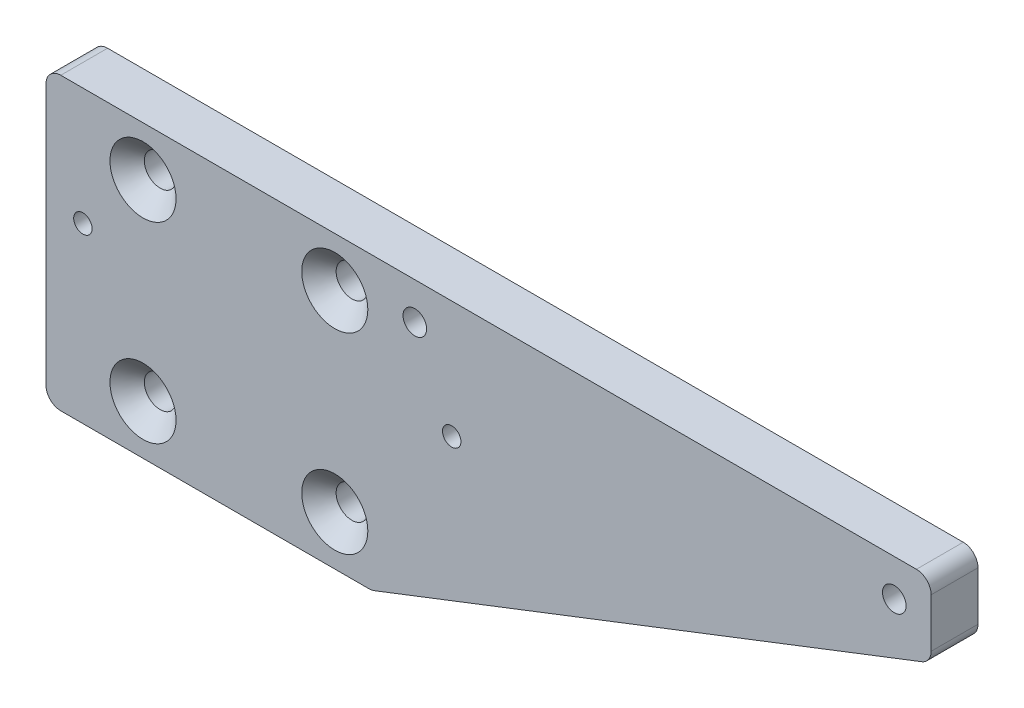
SolidWorks part; units mm, degrees
material "AISI 1045 Steel, cold drawn"
ref_plane "Front Plane" through (0, 0, 0) normal (0, 0, 1) x (1, 0, 0)
ref_plane "Top Plane" through (0, 0, 0) normal (0, 1, 0) x (1, 0, 0)
ref_plane "Right Plane" through (0, 0, 0) normal (1, 0, 0) x (0, 0, -1)
sketch "Sketch1" plane through (0, 0, 0) normal (0, 0, 1) x (1, 0, 0)
  line L0 (22.075, 19.7) -> (97.925, 19.7)
  line L1 (17.075, -13) -> (-8.925, -13) construction
  line L2 (17.075, -13) -> (17.075, 13) construction
  line L3 (17.075, 13) -> (-8.925, 13) construction
  line L4 (-8.925, -13) -> (-8.925, 13) construction
  line L5 (17.075, -13) -> (-8.925, 13) construction
  line L6 (17.075, 13) -> (-8.925, -13) construction
  line L7 (22.075, -19.7) -> (-22.075, -19.7)
  line L8 (22.075, -19.7) -> (22.075, 19.7) construction
  line L9 (22.075, 19.7) -> (-22.075, 19.7)
  line L10 (-22.075, -19.7) -> (-22.075, 19.7)
  line L11 (22.075, -19.7) -> (-22.075, 19.7) construction
  line L12 (22.075, 19.7) -> (-22.075, -19.7) construction
  line L13 (97.925, 19.7) -> (97.925, 9.7)
  line L14 (97.925, 9.7) -> (22.075, -19.7)
  point P0 (4.075, 0)
  point P6 (0, 0)
  point P13 (14.2462, 0.3571)
  dimension "D1" = 39.4
  dimension "D2" = 120
  dimension "D3" = 5
  dimension "D4" = 26
  dimension "D5" = 10
  dimension "D6" = 26.15
extrude "Boss-Extrude1" add sketch "Sketch1" along normal blind 6.35
hole_wizard "CSK for M4 SFHCS2" positions "Sketch2" profile "Sketch3" countersink size "M4" standard "ANSI Metric" end condition through all
sketch "Sketch2" plane through (0, 0, 6.35) normal (0, 0, 1) x (1, 0, 0)
  point P0 (17.075, 13)
  point P3 (-8.925, 13)
sketch "Sketch3" plane through (17.075, 13, 6.35) normal (1, 0, 0) x (0, -1, 0)
  line L0 (0, 0) -> (0, 6.35)
  line L1 (0, 6.35) -> (2.15, 6.35)
  line L2 (2.15, 6.35) -> (2.15, 2.33)
  line L3 (2.15, 2.33) -> (4.48, 0)
  line L5 (4.48, 0) -> (0, 0)
  line L6 (-2.15, 2.33) -> (-4.48, 0) construction
  line L11 (0, -6.35) -> (0, 107.95) construction
  dimension "Thru Hole Dia." = 4.3
  dimension "Thru Hole Depth" = 6.35
  dimension "Near C'Sink Dia." = 8.96
  dimension "Near C'Sink Angle" = 90
hole_wizard "CSK for M4 SFHCS1" positions "Sketch10" profile "Sketch11" countersink size "M4" standard "ANSI Metric" end condition through all
sketch "Sketch10" plane through (0, 0, 6.35) normal (0, 0, 1) x (1, 0, 0)
  point P0 (-8.925, -13)
  point P3 (17.075, -13)
sketch "Sketch11" plane through (-8.925, -13, 6.35) normal (1, 0, 0) x (0, -1, 0)
  line L0 (0, 0) -> (0, 6.35)
  line L1 (0, 6.35) -> (2.15, 6.35)
  line L2 (2.15, 6.35) -> (2.15, 2.33)
  line L3 (2.15, 2.33) -> (4.48, 0)
  line L5 (4.48, 0) -> (0, 0)
  line L6 (-2.15, 2.33) -> (-4.48, 0) construction
  line L11 (0, -6.35) -> (0, 107.95) construction
  dimension "Thru Hole Dia." = 4.3
  dimension "Thru Hole Depth" = 6.35
  dimension "Near C'Sink Dia." = 8.96
  dimension "Near C'Sink Angle" = 90
hole_wizard "Tap Drill for M3x0.5 Tap1" positions "Sketch4" profile "Sketch5" hole size "M3x0.5" standard "ANSI Metric" end condition through all
sketch "Sketch4" plane through (0, 0, 6.35) normal (0, 0, 1) x (1, 0, 0)
  line L0 (-17.075, 3.8) -> (32.925, 3.8) construction
  line L2 (97.925, 19.7) -> (-22.075, 19.7) construction
  line L4 (-22.075, 19.7) -> (-22.075, -19.7) construction
  point P0 (-17.075, 3.8)
  point P2 (32.925, 3.8)
  dimension "D1" = 15.9
  dimension "D2" = 50
  dimension "D3" = 5
sketch "Sketch5" plane through (-17.075, 3.8, 6.35) normal (1, 0, 0) x (0, -1, 0)
  line L0 (0, 0) -> (0, 6.35)
  line L1 (0, 6.35) -> (1.25, 6.35)
  line L2 (1.25, 6.35) -> (1.25, 0)
  line L5 (1.25, 0) -> (0, 0)
  line L11 (0, -6.35) -> (0, 107.95) construction
  dimension "Thru Hole Dia." = 2.5
  dimension "Thru Hole Depth" = 6.35
hole_wizard "M3 Clearance Hole2" positions "Sketch7" profile "Sketch9" hole size "M3" standard "ANSI Metric" end condition through all
sketch "Sketch7" plane through (0, 0, 0) normal (0, 0, -1) x (-1, 0, 0)
  line L1 (-92.925, 14.7) -> (-27.925, 14.7) construction
  line L3 (-97.925, 9.7) -> (-97.925, 19.7) construction
  line L4 (22.075, 19.7) -> (22.075, -19.7) construction
  point P0 (-92.925, 14.7)
  point P2 (-27.925, 14.7)
  point P21 (-97.925, 14.7)
  dimension "D1" = 115
  dimension "D2" = 65
sketch "Sketch9" plane through (92.925, 14.7, 0) normal (1, 0, 0) x (0, 1, 0)
  line L0 (0, 0) -> (0, 6.35)
  line L1 (0, 6.35) -> (1.6, 6.35)
  line L2 (1.6, 6.35) -> (1.6, 0)
  line L5 (1.6, 0) -> (0, 0)
  line L11 (0, -6.35) -> (0, 107.95) construction
  dimension "Thru Hole Dia." = 3.2
  dimension "Thru Hole Depth" = 6.35
fillet "Fillet1" radius 2 5 edges at (22.075, -19.7, 3.175) (-22.075, -19.7, 3.175) (97.925, 19.7, 3.175) (-22.075, 19.7, 3.175) (97.925, 9.7, 3.175)
